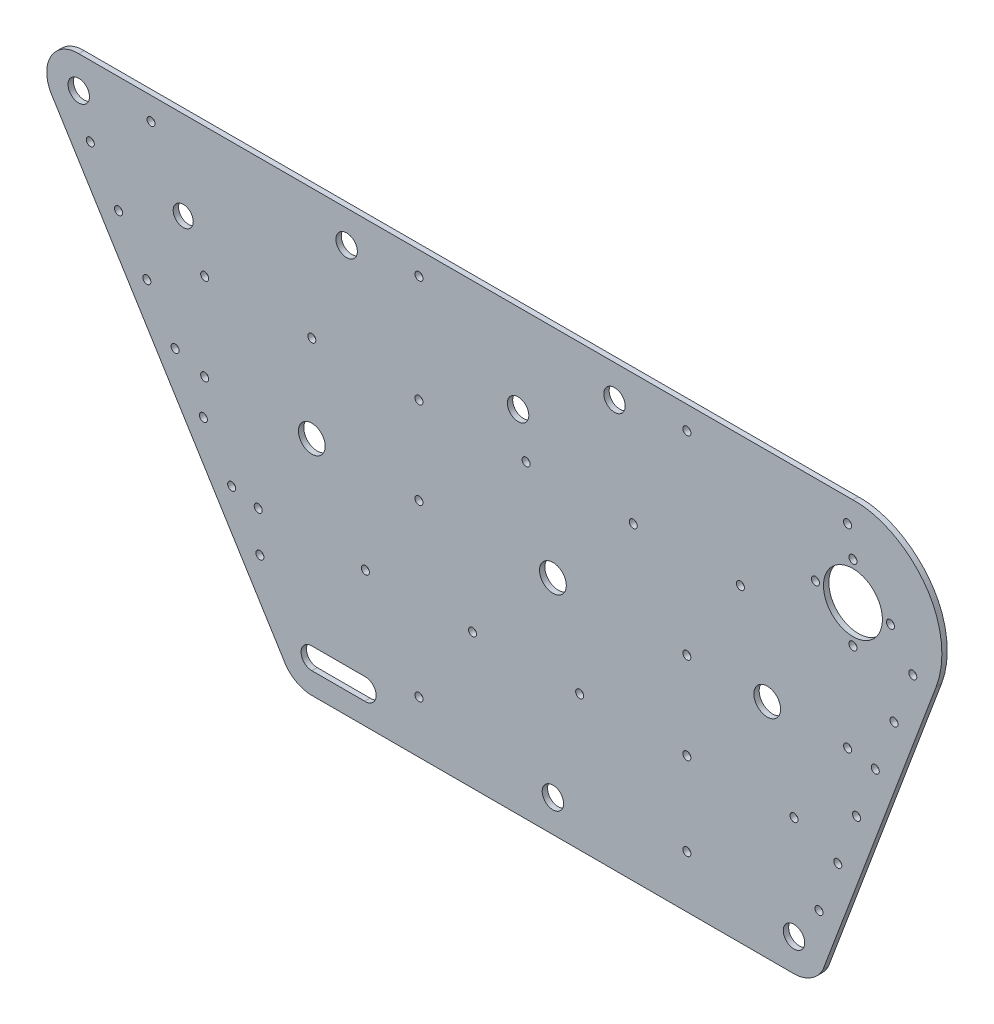
SolidWorks part; units mm, degrees
ref_plane "Front Plane" through (0, 0, 0) normal (0, 0, 1) x (1, 0, 0)
ref_plane "Top Plane" through (0, 0, 0) normal (0, 1, 0) x (1, 0, 0)
ref_plane "Right Plane" through (0, 0, 0) normal (1, 0, 0) x (0, 0, -1)
sketch "Sketch2" plane through (0, 0, 0) normal (0, 0, 1) x (1, 0, 0)
  line L0 (-106.0052, 144.9436) -> (182.9631, 145.1977)
  line L1 (160.992, -19) -> (-18.999, -19)
  line L2 (171.9001, -12) -> (214.069, 100.3323)
  line L3 (-18.999, -3) -> (1, -3)
  line L4 (0.9999, -11) -> (-18.9991, -11)
  line L5 (-29.7001, -12.4286) -> (-116.0855, 126.6112)
  line L6 (-18.9991, -18) -> (-18.8768, -17.9993)
  ellipse E0 centre (-105.9947, 133) end of major axis (-105.9947, 137) minor radius 3.9998
  ellipse E1 centre (160.992, -7) end of major axis (160.992, -3) minor radius 3.9998
  ellipse E2 centre (-18.9991, -7) end of major axis (-18.9991, -11) minor radius 3.9998 (-18.999, -3) -> (-18.9991, -11) ccw
  ellipse E3 centre (182.9908, 112) end of major axis (182.9908, 123) minor radius 10.9995
  ellipse E4 centre (-105.9947, 133) end of major axis (-105.9947, 144.9436) minor radius 11.943 (-106.0052, 144.9436) -> (-116.0855, 126.6112) ccw
  ellipse E5 centre (182.9908, 112) end of major axis (182.9909, 145.1977) minor radius 33.196 (214.069, 100.3323) -> (182.9617, 145.1977) ccw
  ellipse E6 centre (1, -7) end of major axis (1, -3) minor radius 3.9998 (0.9999, -11) -> (1, -3) ccw
  ellipse E7 centre (182.9908, 126) end of major axis (182.9908, 127.5) minor radius 1.4999
  ellipse E8 centre (196.9901, 112) end of major axis (196.9901, 113.5) minor radius 1.4999
  ellipse E9 centre (168.9915, 112) end of major axis (168.9915, 113.5) minor radius 1.4999
  ellipse E10 centre (182.9908, 98) end of major axis (182.9908, 99.5) minor radius 1.4999
  ellipse E11 centre (-18.9991, -7) end of major axis (-18.999, 5) minor radius 11.9994 (-29.7019, -12.4256) -> (-18.999, -19) ccw
  ellipse E12 centre (160.992, -7) end of major axis (160.992, 5) minor radius 11.9994 (160.992, -19) -> (171.9001, -12) ccw
  ellipse E13 centre (120.9939, 0.5) end of major axis (120.994, 2) minor radius 1.4999
  ellipse E14 centre (20.9989, 0.5) end of major axis (20.9989, 2) minor radius 1.4999
  ellipse E15 centre (120.9939, 64) end of major axis (120.994, 65.5) minor radius 1.4999
  ellipse E16 centre (20.9989, 64) end of major axis (20.9989, 65.5) minor radius 1.4999
  ellipse E17 centre (-58.997, 64) end of major axis (-58.997, 65.5) minor radius 1.4999
  ellipse E18 centre (180.9909, 64) end of major axis (180.9909, 65.5) minor radius 1.4999
  ellipse E19 centre (-78.996, 136.5) end of major axis (-78.996, 138) minor radius 1.4999
  ellipse E20 centre (20.9989, 136.5) end of major axis (20.9989, 138) minor radius 1.4999
  ellipse E21 centre (120.9939, 136.5) end of major axis (120.994, 138) minor radius 1.4999
  ellipse E22 centre (60.9969, 96.5) end of major axis (60.9969, 98) minor radius 1.4999
  ellipse E23 centre (140.9929, 96.5) end of major axis (140.9929, 98) minor radius 1.4999
  ellipse E24 centre (160.992, 31.5) end of major axis (160.992, 33) minor radius 1.4999
  ellipse E25 centre (80.996, 31.5) end of major axis (80.996, 33) minor radius 1.4999
  ellipse E26 centre (-18.9991, 96.5) end of major axis (-18.9991, 98) minor radius 1.4999
  ellipse E27 centre (-38.998, 31.5) end of major axis (-38.998, 33) minor radius 1.4999
  ellipse E28 centre (-18.9991, 64) end of major axis (-18.999, 69) minor radius 4.9997
  ellipse E29 centre (70.9964, 64) end of major axis (70.9965, 69) minor radius 4.9997
  ellipse E30 centre (150.9924, 64) end of major axis (150.9924, 69) minor radius 4.9997
  ellipse E31 centre (-101.6892, 118.5984) end of major axis (-101.6892, 120.0984) minor radius 1.4999
  ellipse E32 centre (-91.1347, 101.6106) end of major axis (-91.1347, 103.1106) minor radius 1.4999
  ellipse E33 centre (-80.5803, 84.623) end of major axis (-80.5803, 86.123) minor radius 1.4999
  ellipse E34 centre (-70.0255, 67.6347) end of major axis (-70.0255, 69.1347) minor radius 1.4999
  ellipse E35 centre (-59.4708, 50.6466) end of major axis (-59.4708, 52.1466) minor radius 1.4999
  ellipse E36 centre (-48.9163, 33.6588) end of major axis (-48.9163, 35.1588) minor radius 1.4999
  ellipse E37 centre (-38.3619, 16.6713) end of major axis (-38.3619, 18.1713) minor radius 1.4999
  ellipse E38 centre (205.3225, 99.7958) end of major axis (205.3225, 101.2958) minor radius 1.4999
  ellipse E39 centre (198.3244, 81.0602) end of major axis (198.3244, 82.5602) minor radius 1.4999
  ellipse E40 centre (191.3265, 62.3248) end of major axis (191.3265, 63.8248) minor radius 1.4999
  ellipse E41 centre (184.3286, 43.5896) end of major axis (184.3286, 45.0896) minor radius 1.4999
  ellipse E42 centre (177.3307, 24.8545) end of major axis (177.3307, 26.3545) minor radius 1.4999
  ellipse E43 centre (170.3325, 6.1186) end of major axis (170.3325, 7.6186) minor radius 1.4999
  ellipse E44 centre (180.9909, 136.5) end of major axis (180.9909, 138) minor radius 1.4999
  ellipse E45 centre (20.9989, 96.5) end of major axis (20.9989, 98) minor radius 1.4999
  ellipse E46 centre (100.995, 96.5) end of major axis (100.995, 98) minor radius 1.4999
  ellipse E47 centre (-58.9971, 96.5) end of major axis (-58.997, 98) minor radius 1.4999
  ellipse E48 centre (0.9999, 31.5) end of major axis (1, 33) minor radius 1.4999
  ellipse E49 centre (40.9979, 31.5) end of major axis (40.9979, 33) minor radius 1.4999
  ellipse E50 centre (120.9939, 31.5) end of major axis (120.994, 33) minor radius 1.4999
  ellipse E51 centre (-66.9967, 112) end of major axis (-66.9966, 115.75) minor radius 3.7498
  ellipse E52 centre (57.9971, 112) end of major axis (57.9971, 116) minor radius 3.9998
  ellipse E53 centre (-5.9997, 133) end of major axis (-5.9997, 137) minor radius 3.9998
  ellipse E54 centre (93.9952, 133) end of major axis (93.9952, 137) minor radius 3.9998
  ellipse E55 centre (70.9964, -7) end of major axis (70.9965, -3) minor radius 3.9998
sketch "Sketch3" plane through (0, 0, 0) normal (0, 0, 1) x (1, 0, 0)
  line L0 (-106.0052, 144.9436) -> (182.9631, 145.1977)
  line L1 (214.069, 100.3323) -> (171.9001, -12)
  line L2 (160.992, -19) -> (-18.999, -19)
  line L3 (-29.7019, -12.4256) -> (-116.0855, 126.6112)
  ellipse E0 centre (182.9908, 112) end of major axis (182.9909, 145.1977) minor radius 33.196 (214.069, 100.3323) -> (182.9617, 145.1977) ccw construction
  ellipse E1 centre (160.992, -7) end of major axis (160.992, 5) minor radius 11.9994 (160.992, -19) -> (171.9001, -12) ccw construction
  ellipse E2 centre (-18.9991, -7) end of major axis (-18.999, 5) minor radius 11.9994 (-29.7019, -12.4256) -> (-18.999, -19) ccw construction
  ellipse E3 centre (-105.9947, 133) end of major axis (-105.9947, 144.9436) minor radius 11.943 (-106.0052, 144.9436) -> (-116.0855, 126.6112) ccw construction
  spline S0 degree 3 poles (214.069, 100.3323) (217.2028, 108.5816) (216.3843, 131.5138) (195.3828, 145.6087) (182.9631, 145.1977) knots 0 0 0 0 0.416239 1 1 1 1
  spline S1 degree 3 poles (160.992, -19) (165.4579, -19.0688) (170.107, -16.0905) (171.9001, -12) knots 0 0 0 0 1 1 1 1
  spline S2 degree 3 poles (-18.999, -19) (-23.4193, -19.0696) (-27.756, -16.3629) (-29.7019, -12.4256) knots 0 0 0 0 1 1 1 1
  spline S3 degree 3 poles (-106.0052, 144.9436) (-112.924, 145.0927) (-119.6619, 137.0318) (-117.3485, 128.5923) (-116.0855, 126.6112) knots 0 0 0 0 0.715346 1 1 1 1
extrude "Boss-Extrude1" add sketch "Sketch3" along normal blind 2
sketch "Sketch4" plane through (0, 0, 2) normal (0, 0, 1) x (1, 0, 0)
  line L0 (-18.999, -3) -> (1, -3)
  line L2 (-18.9991, -11) -> (0.7423, -11)
  line L3 (0.9999, -11) -> (-18.9991, -11) construction
  circle A0 centre (-105.9947, 133) radius 3.9998
  circle A1 centre (-78.996, 136.5) radius 1.4999
  circle A2 centre (-101.6892, 118.5984) radius 1.4999
  circle A3 centre (-91.1347, 101.6106) radius 1.4999
  circle A4 centre (-66.9967, 112) radius 3.7498
  circle A5 centre (-80.5803, 84.623) radius 1.4999
  circle A6 centre (-5.9997, 133) radius 3.9998
  circle A7 centre (20.9989, 136.5) radius 1.4999
  circle A8 centre (20.9989, 96.5) radius 1.4999
  circle A9 centre (-18.9991, 96.5) radius 1.4999
  circle A10 centre (-58.9971, 96.5) radius 1.4999
  circle A11 centre (57.9971, 112) radius 3.9998
  circle A12 centre (60.9969, 96.5) radius 1.4999
  circle A13 centre (182.9908, 112) radius 10.9995
  circle A14 centre (182.9908, 126) radius 1.4999
  circle A15 centre (180.9909, 136.5) radius 1.4999
  circle A16 centre (120.9939, 136.5) radius 1.4999
  circle A17 centre (93.9952, 133) radius 3.9998
  circle A18 centre (100.995, 96.5) radius 1.4999
  circle A19 centre (140.9929, 96.5) radius 1.4999
  circle A20 centre (168.9915, 112) radius 1.4999
  circle A21 centre (196.9901, 112) radius 1.4999
  circle A22 centre (182.9908, 98) radius 1.4999
  circle A23 centre (205.3225, 99.7958) radius 1.4999
  circle A24 centre (198.3244, 81.0602) radius 1.4999
  circle A25 centre (150.9924, 64) radius 4.9997
  circle A26 centre (180.9909, 64) radius 1.4999
  circle A27 centre (191.3265, 62.3248) radius 1.4999
  circle A28 centre (120.9939, 64) radius 1.4999
  circle A29 centre (184.3286, 43.5896) radius 1.4999
  circle A30 centre (70.9964, 64) radius 4.9997
  circle A31 centre (20.9989, 64) radius 1.4999
  circle A32 centre (0.9999, 31.5) radius 1.4999
  circle A33 centre (40.9979, 31.5) radius 1.4999
  circle A34 centre (80.996, 31.5) radius 1.4999
  circle A35 centre (120.9939, 31.5) radius 1.4999
  circle A36 centre (160.992, 31.5) radius 1.4999
  circle A37 centre (177.3307, 24.8545) radius 1.4999
  circle A38 centre (-18.9991, 64) radius 4.9997
  circle A39 centre (-70.0255, 67.6347) radius 1.4999
  circle A40 centre (-58.997, 64) radius 1.4999
  circle A41 centre (-59.4708, 50.6466) radius 1.4999
  circle A42 centre (-48.9163, 33.6588) radius 1.4999
  circle A43 centre (-38.998, 31.5) radius 1.4999
  circle A44 centre (-38.3619, 16.6713) radius 1.4999
  circle A45 centre (20.9989, 0.5) radius 1.4999
  circle A46 centre (70.9964, -7) radius 3.9998
  circle A47 centre (160.992, -7) radius 3.9998
  circle A48 centre (170.3325, 6.1186) radius 1.4999
  circle A49 centre (120.9939, 0.5) radius 1.4999
  arc A50 (-18.999, -3) -> (-18.9991, -11) centre (-18.9988, -7) ccw
  arc A51 (1, -3) -> (0.7423, -11) centre (0.9957, -7.004) cw
extrude "Cut-Extrude1" cut sketch "Sketch4" against normal blind 2
